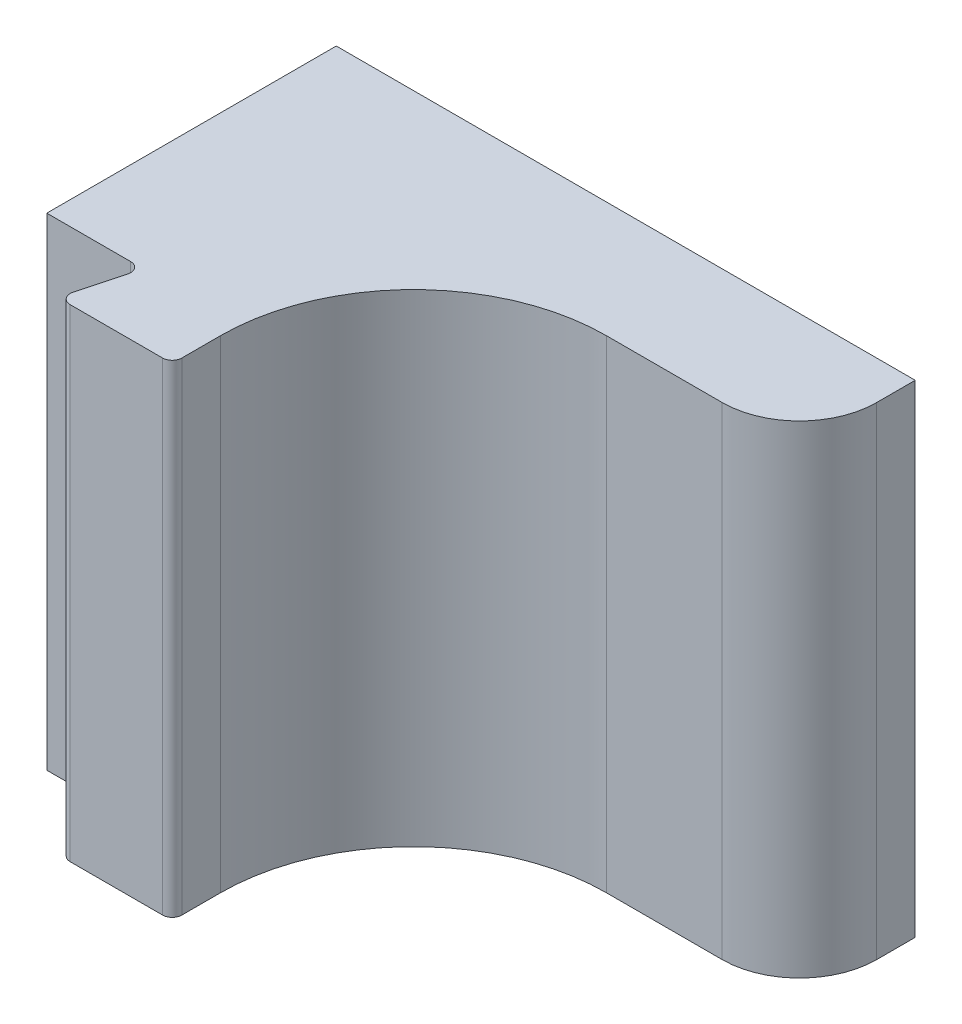
SolidWorks part; units mm, degrees
ref_plane "Top" through (0, 0, 0) normal (0, 0, 1) x (1, 0, 0)
ref_plane "Front" through (0, 0, 0) normal (0, 1, 0) x (1, 0, 0)
ref_plane "Right" through (0, 0, 0) normal (1, 0, 0) x (0, 0, -1)
sketch "Profile Sketch" plane through (-14.3347, 0, -24.6701) normal (0, 1, 0) x (-1, 0, 0)
  line L1 (0.6653, 24.6701) -> (-29.3347, 24.6701)
  line L2 (-9.3347, 30.6701) -> (-9.3347, 43.1701)
  line L3 (-9.3347, 43.1701) -> (-3.3969, 43.1701)
  line L4 (-3.3969, 43.1701) -> (-4.3347, 39.6701)
  line L5 (-4.3347, 39.6701) -> (0.6653, 39.6701)
  line L7 (-4.3347, 39.6701) -> (-4.3347, 24.6701) construction
  line L8 (0.6653, 39.6701) -> (0.6653, 24.6701)
  line L9 (-9.3347, 30.6701) -> (-29.3347, 30.6701)
  line L10 (-29.3347, 30.6701) -> (-29.3347, 24.6701)
  dimension "D1" = 3.5
  dimension "D2" = 5
  dimension "D3" = 6
  dimension "D4" = 75
  dimension "D5" = 10
  dimension "D6" = 30
  dimension "D7" = 15
extrude "Length Extrude" add sketch "Profile Sketch" along normal mid plane 25
fillet "Edge Fillets" radius 0.5 3 edges at (-10.9378, 0, 18.5) (-10, 0, 15) (-5, 0, 18.5)
fillet "Base Fillet" radius 4 1 edges at (15, 0, 6)
fillet "Transition Fillet" radius 10 1 edges at (-5, 0, 6)
sketch "Magnet Slot Sketch" plane through (0, 0, 0) normal (0, 0, -1) x (-1, 0, 0)
  line L0 (-8.5, -12.5) -> (-8.5, 0) construction
  line L1 (-15, -12.5) -> (15, -12.5) construction
  line L2 (-7.386, -3.4374) -> (-7.6428, -3.01)
  line L5 (-11.4249, -2.1217) -> (-11.0978, -1.7453)
  line L7 (-11.4217, 2.1261) -> (-10.9627, 1.9313)
  line L9 (-7.3808, 3.4357) -> (-7.4243, 2.9389)
  line L14 (-15, 0) -> (-8.5, 0) construction
  line L16 (-15, 12.5) -> (-15, -12.5) construction
  line L17 (-15, -12.5) -> (15, -12.5) construction
  line L18 (-4.8866, -0.0027) -> (-5.3725, -0.1149)
  line L20 (-5.9022, -1.7453) -> (-5.5751, -2.1217)
  line L24 (-8.5, 0) -> (-5.8403, -3.6608) construction
  line L25 (-9.3572, -3.01) -> (-9.614, -3.4374)
  line L26 (-11.6275, -0.1149) -> (-12.1134, -0.0027)
  line L27 (-9.5757, 2.9389) -> (-9.6192, 3.4357)
  line L28 (-6.0373, 1.9313) -> (-5.5783, 2.1261)
  arc A1 (-5.9696, -3.7514) -> (-7.386, -3.4374) centre (-6.5288, -2.9224) cw
  arc A2 (-7.6428, -3.01) -> (-9.3572, -3.01) centre (-8.5, -3.525) ccw
  circle A4 centre (-8.5, 0) radius 2.525 construction
  arc A6 (-11.0978, -1.7453) -> (-11.6275, -0.1149) centre (-11.8525, -1.0893) ccw
  arc A7 (-11.2859, -3.5658) -> (-11.4249, -2.1217) centre (-10.6702, -2.7777) cw
  arc A9 (-10.9627, 1.9313) -> (-9.5757, 2.9389) centre (-10.5719, 2.8518) ccw
  arc A10 (-12.7521, 1.5476) -> (-11.4217, 2.1261) centre (-11.8124, 1.2056) cw
  arc A12 (-7.4243, 2.9389) -> (-6.0373, 1.9313) centre (-6.4281, 2.8518) ccw
  arc A13 (-8.3421, 4.5222) -> (-7.3808, 3.4357) centre (-8.377, 3.5229) cw
  arc A29 (-5.3725, -0.1149) -> (-5.9022, -1.7453) centre (-5.1475, -1.0893) ccw
  arc A30 (-4.1503, 1.2473) -> (-4.8866, -0.0027) centre (-5.1116, 0.9716) cw
  arc A36 (-5.9696, -3.7514) -> (-5.7141, -3.5658) centre (-8.5, 0) ccw
  arc A37 (-5.7141, -3.5658) -> (-5.5751, -2.1217) centre (-6.3298, -2.7777) ccw
  arc A38 (-11.2859, -3.5658) -> (-11.0304, -3.7514) centre (-8.5, 0) ccw
  arc A39 (-11.0304, -3.7514) -> (-9.614, -3.4374) centre (-10.4712, -2.9224) ccw
  circle A40 centre (-8.5, 0) radius 4.525 construction
  arc A41 (-12.7521, 1.5476) -> (-12.8497, 1.2473) centre (-8.5, 0) ccw
  arc A42 (-12.8497, 1.2473) -> (-12.1134, -0.0027) centre (-11.8884, 0.9716) ccw
  arc A43 (-8.3421, 4.5222) -> (-8.6579, 4.5222) centre (-8.5, 0) ccw
  arc A44 (-8.6579, 4.5222) -> (-9.6192, 3.4357) centre (-8.623, 3.5229) ccw
  arc A45 (-4.1503, 1.2473) -> (-4.2479, 1.5476) centre (-8.5, 0) ccw
  arc A46 (-4.2479, 1.5476) -> (-5.5783, 2.1261) centre (-5.1876, 1.2056) ccw
  point P45 (0, -12.5)
  dimension "D1" = 8.5
  dimension "D2" = 2
  dimension "D3" = 5.05
  dimension "D4" = 1
  dimension "D5" = 1
  dimension "D7" = 5
  dimension "D6" = 5
extrude "Magnet Slot Cut" cut sketch "Magnet Slot Sketch" against normal blind 4
chamfer "Magnet Slot Chamfer" distance 0.475 angle 45 30 edges at (7.4025, 3.1873, 0) (7.628, 4.1855, 0) (7.0158, 2.0428, 0) (9.9842, 2.0428, 0) (11.1922, 2.0287, 0) (12.2112, 2.1227, 0) (10.9014, -0.7803, 0) (11.2613, -1.9335, 0) (11.6656, -2.8736, 0) (8.5, -2.525, 0) (6.7453, -3.8986, 0) (7.5144, -3.2237, 0) (4.2499, 0.4641, 0) (5.1295, -0.0588, 0) (6.0986, -0.7803, 0) (9.372, 4.1855, 0) (9.5975, 3.1873, 0) (8.5, 4.525, 0) (12.8035, 1.3983, 0) (5.8078, 2.0287, 0) (12.7501, 0.4641, 0) (4.7888, 2.1227, 0) (11.8705, -0.0588, 0) (4.1965, 1.3983, 0) (11.1597, -3.6608, 0) (5.7387, -1.9335, 0) (10.2547, -3.8986, 0) (5.3344, -2.8736, 0) (9.4856, -3.2237, 0) (5.8403, -3.6608, 0)
mirror "Magnet Hole Mirror" about plane through (0, 0, 0) normal (1, 0, 0) of "Magnet Slot Chamfer", "Magnet Slot Cut"
other "Magnet Holes Fill Pattern" [suppressed] parameters "D5"=0, "D6"=0, "D4"=30, "D9"=3, "D3"=0, "D7"=0, "D8"=0
